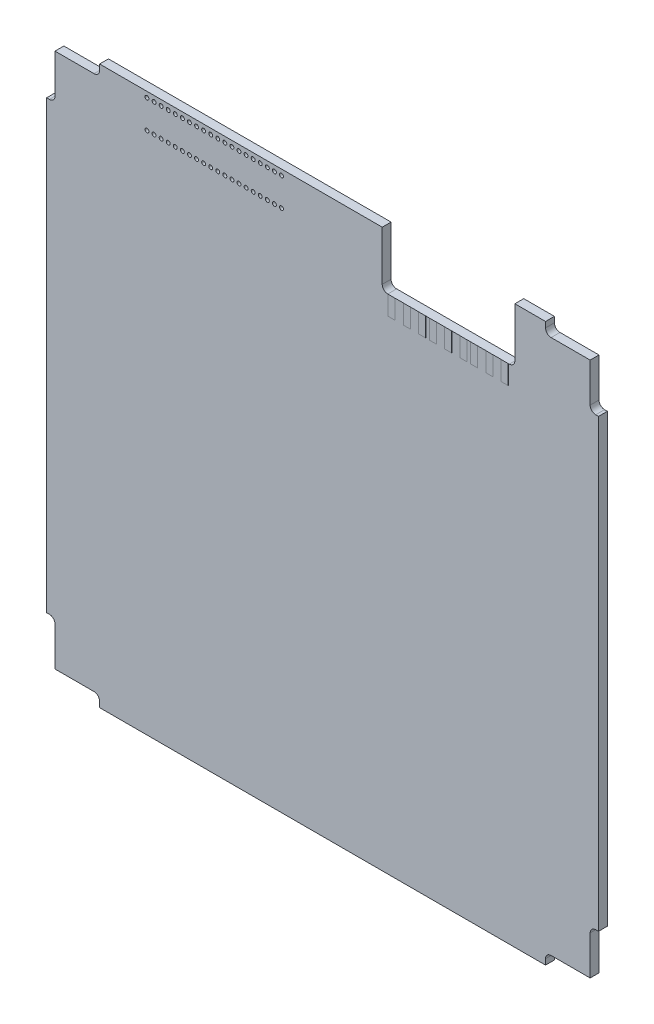
SolidWorks part; units mm, degrees
material "ABS"
ref_plane "Front Plane" through (0, 0, 0) normal (0, 0, 1) x (1, 0, 0)
ref_plane "Top Plane" through (0, 0, 0) normal (0, 1, 0) x (1, 0, 0)
ref_plane "Right Plane" through (0, 0, 0) normal (1, 0, 0) x (0, 0, -1)
sketch "Sketch1" plane through (0, 0, 0) normal (0, 0, 1) x (1, 0, 0)
  line L0 (-40, 50) -> (-40, 48)
  line L1 (-50, -50) -> (50, -50)
  line L2 (-50, -50) -> (-50, 50)
  line L3 (-50, 50) -> (50, 50)
  line L4 (50, -50) -> (50, 50)
  line L5 (-50, -50) -> (50, 50) construction
  line L6 (-50, 50) -> (50, -50) construction
  line L7 (-50, 50) -> (-40, 50)
  line L8 (-50, 50) -> (-50, 40)
  line L9 (-40, 48) -> (-48, 48)
  line L10 (-48, 48) -> (-48, 40)
  line L11 (50, 50) -> (40, 50)
  line L12 (50, 50) -> (50, 40)
  line L13 (-48, 40) -> (-50, 40)
  line L14 (50, 40) -> (48, 40)
  line L15 (-50, -50) -> (-37.8649, -50)
  line L16 (-50, -50) -> (-50, -37.8649)
  line L17 (50, 50) -> (50, 40)
  line L18 (50, 50) -> (40, 50)
  line L19 (50, -50) -> (41.5, -50)
  line L20 (50, -50) -> (50, -41.5)
  line L21 (48, 40) -> (48, 48)
  line L22 (48, 48) -> (40, 48)
  line L23 (40, 48) -> (40, 50)
  line L24 (40, -50) -> (40, -48)
  line L25 (50, -50) -> (40, -50)
  line L26 (50, -50) -> (50, -40)
  line L27 (40, -48) -> (48, -48)
  line L28 (48, -48) -> (48, -40)
  line L29 (48, -40) -> (50, -40)
  line L30 (-50, -40) -> (-48, -40)
  line L31 (-50, -50) -> (-50, -40)
  line L32 (-50, -50) -> (-40, -50)
  line L33 (-48, -40) -> (-48, -48)
  line L34 (-48, -48) -> (-40, -48)
  line L35 (-40, -48) -> (-40, -50)
  point P0 (0, 0)
  point P38 (0, 0)
  dimension "D1" = 100
  dimension "D2" = 100
  dimension "D3" = 2
  dimension "D4" = 10
  dimension "D5" = 4
extrude "Boss-Extrude1" add sketch "Sketch1" along normal blind 1.5875 contours L1 L4 L3 L2 region at (0, 0, 0)
fillet "Fillet1" radius 1 8 edges at (-48, -40, 0.7937) (-40, -48, 0.7937) (40, -48, 0.7937) (48, -40, 0.7937) (48, 40, 0.7937) (40, 48, 0.7937) (-40, 48, 0.7937) (-48, 40, 0.7937)
sketch "Sketch2" plane through (0, 0, 1.5875) normal (0, 0, 1) x (1, 0, 0)
  line L0 (0, 50) -> (0, -50) construction
  line L1 (-40, 50) -> (40, 50) construction
  line L2 (-40, -50) -> (40, -50) construction
  line L3 (-50, -40) -> (-50, 40) construction
  line L4 (-40, 50) -> (40, 50) construction
  circle A0 centre (-31.5, 49) radius 0.35
  circle A1 centre (-30.23, 49) radius 0.35
  circle A2 centre (-28.96, 49) radius 0.35
  circle A3 centre (-27.69, 49) radius 0.35
  circle A4 centre (-26.42, 49) radius 0.35
  circle A5 centre (-25.15, 49) radius 0.35
  circle A6 centre (-23.88, 49) radius 0.35
  circle A7 centre (-22.61, 49) radius 0.35
  circle A8 centre (-21.34, 49) radius 0.35
  circle A9 centre (-20.07, 49) radius 0.35
  circle A10 centre (-18.8, 49) radius 0.35
  circle A11 centre (-17.53, 49) radius 0.35
  circle A12 centre (-16.26, 49) radius 0.35
  circle A13 centre (-14.99, 49) radius 0.35
  circle A14 centre (-13.72, 49) radius 0.35
  circle A15 centre (-12.45, 49) radius 0.35
  circle A16 centre (-11.18, 49) radius 0.35
  circle A17 centre (-9.91, 49) radius 0.35
  circle A18 centre (-8.64, 49) radius 0.35
  circle A19 centre (-7.37, 49) radius 0.35
  circle A20 centre (-30.23, 43.92) radius 0.35
  circle A21 centre (-28.96, 43.92) radius 0.35
  circle A22 centre (-27.69, 43.92) radius 0.35
  circle A23 centre (-26.42, 43.92) radius 0.35
  circle A24 centre (-25.15, 43.92) radius 0.35
  circle A25 centre (-23.88, 43.92) radius 0.35
  circle A26 centre (-22.61, 43.92) radius 0.35
  circle A27 centre (-21.34, 43.92) radius 0.35
  circle A28 centre (-20.07, 43.92) radius 0.35
  circle A29 centre (-18.8, 43.92) radius 0.35
  circle A30 centre (-17.53, 43.92) radius 0.35
  circle A31 centre (-16.26, 43.92) radius 0.35
  circle A32 centre (-14.99, 43.92) radius 0.35
  circle A33 centre (-13.72, 43.92) radius 0.35
  circle A34 centre (-12.45, 43.92) radius 0.35
  circle A35 centre (-11.18, 43.92) radius 0.35
  circle A36 centre (-9.91, 43.92) radius 0.35
  circle A37 centre (-8.64, 43.92) radius 0.35
  circle A38 centre (-7.37, 43.92) radius 0.35
  circle A39 centre (-31.5, 43.92) radius 0.35
  dimension "D1" = 0.7
  dimension "D4" = 18.5
  dimension "D5" = 1
  dimension "D2" = 5.08
  dimension "D3" = 1.27
extrude "Cut-Extrude1" cut sketch "Sketch2" against normal through all
sketch "Sketch3" plane through (0, 50, 0) normal (0, 1, 0) x (1, 0, 0)
  line L0 (-40, 0) -> (40, 0) construction
  line L1 (10.7, 0) -> (19.7, 0)
  line L2 (10.7, 0) -> (10.7, -1.5875)
  line L3 (10.7, -1.5875) -> (19.7, -1.5875)
  line L4 (-40, -1.5875) -> (-40, 0) construction
  line L5 (-40, -1.5875) -> (40, -1.5875) construction
  line L6 (15.2, 0) -> (15.2, -1.5875) construction
  line L7 (12, 0) -> (12, -1.5875) construction
  line L8 (18.4, 0) -> (18.4, -1.5875) construction
  line L9 (-40, -1.5875) -> (40, -1.5875) construction
  line L12 (19.7, 0) -> (34.5, 0)
  line L14 (19.7, -1.5875) -> (34.5, -1.5875)
  line L15 (34.5, 0) -> (34.5, -1.5875)
  dimension "D1" = 9
  dimension "D2" = 6.4
  dimension "D3" = 3.2
  dimension "D5" = 14.8
  dimension "D6" = 50.7
extrude "Cut-Extrude2" cut sketch "Sketch3" against normal blind 9.8806
fillet "Fillet2" radius 1 2 edges at (10.7, 40.1194, 0.7938) (34.5, 40.1194, 0.7937)
sketch "Sketch5" plane through (0, 0, 0) normal (0, 0, -1) x (-1, 0, 0)
  line L0 (40, -50) -> (-40, -50) construction
  line L1 (-49.5, 50) -> (49.5, 50)
  line L2 (-49.5, 50) -> (-49.5, -50)
  line L3 (-49.5, -50) -> (49.5, -50)
  line L4 (49.5, 50) -> (49.5, -50)
  line L5 (40, 50) -> (-10.7, 50) construction
  line L6 (50, -40) -> (50, 40) construction
  dimension "D1" = 99
  dimension "D2" = 0.5
extrude "Cut-Extrude3" cut sketch "Sketch5" against normal through all flip side to cut
sketch "Sketch6" plane through (0, 0, 1.5875) normal (0, 0, 1) x (1, 0, 0)
  line L0 (12.4, 40.1194) -> (12.4, 36.6894) construction
  line L1 (11.765, 40.1194) -> (13.035, 40.1194)
  line L2 (11.765, 40.1194) -> (11.765, 36.6894)
  line L3 (11.765, 36.6894) -> (13.035, 36.6894)
  line L4 (13.035, 40.1194) -> (13.035, 36.6894)
  line L5 (14.505, 40.1194) -> (15.775, 40.1194)
  line L6 (14.505, 40.1194) -> (14.505, 36.6894)
  line L7 (14.505, 36.6894) -> (15.775, 36.6894)
  line L8 (15.775, 40.1194) -> (15.775, 36.6894)
  line L9 (17.245, 40.1194) -> (18.515, 40.1194)
  line L10 (17.245, 40.1194) -> (17.245, 36.6894)
  line L11 (17.245, 36.6894) -> (18.515, 36.6894)
  line L12 (18.515, 40.1194) -> (18.515, 36.6894)
  line L13 (15.14, 40.1194) -> (15.14, 36.6894) construction
  line L14 (17.88, 40.1194) -> (17.88, 36.6894) construction
  line L15 (11.7, 40.1194) -> (33.5, 40.1194) construction
  line L16 (12.8, 36.9194) -> (12, 36.9194) construction
  line L17 (19.165, 40.1194) -> (20.435, 40.1194)
  line L18 (19.165, 40.1194) -> (19.165, 36.6894)
  line L19 (19.165, 36.6894) -> (20.435, 36.6894)
  line L20 (20.435, 40.1194) -> (20.435, 36.6894)
  line L21 (21.905, 40.1194) -> (23.175, 40.1194)
  line L22 (21.905, 40.1194) -> (21.905, 36.6894)
  line L23 (21.905, 36.6894) -> (23.175, 36.6894)
  line L24 (23.175, 40.1194) -> (23.175, 36.6894)
  line L25 (24.645, 40.1194) -> (25.915, 40.1194)
  line L26 (24.645, 40.1194) -> (24.645, 36.6894)
  line L27 (24.645, 36.6894) -> (25.915, 36.6894)
  line L28 (25.915, 40.1194) -> (25.915, 36.6894)
  line L29 (19.8, 40.1194) -> (19.8, 36.6894) construction
  line L30 (22.54, 40.1194) -> (22.54, 36.6894) construction
  line L31 (25.28, 40.1194) -> (25.28, 36.6894) construction
  line L32 (26.565, 40.1194) -> (27.835, 40.1194)
  line L33 (26.565, 40.1194) -> (26.565, 36.6894)
  line L34 (26.565, 36.6894) -> (27.835, 36.6894)
  line L35 (27.835, 40.1194) -> (27.835, 36.6894)
  line L36 (29.305, 40.1194) -> (30.575, 40.1194)
  line L37 (29.305, 40.1194) -> (29.305, 36.6894)
  line L38 (29.305, 36.6894) -> (30.575, 36.6894)
  line L39 (30.575, 40.1194) -> (30.575, 36.6894)
  line L40 (32.045, 40.1194) -> (33.315, 40.1194)
  line L41 (32.045, 40.1194) -> (32.045, 36.6894)
  line L42 (32.045, 36.6894) -> (33.315, 36.6894)
  line L43 (33.315, 40.1194) -> (33.315, 36.6894)
  line L44 (27.2, 40.1194) -> (27.2, 36.6894) construction
  line L45 (29.94, 40.1194) -> (29.94, 36.6894) construction
  line L46 (32.68, 40.1194) -> (32.68, 36.6894) construction
  point P20 (12.4, 36.9194)
  point P42 (19.8, 36.9194)
  point P61 (27.2, 36.9194)
  dimension "D1" = 1.27
  dimension "D2" = 3.43
  dimension "D3" = 2.74
  dimension "D4" = 2.74
  dimension "D6" = 7.4
  dimension "D5" = 3
extrude "Boss-Extrude2" add sketch "Sketch6" along normal blind 0.01
